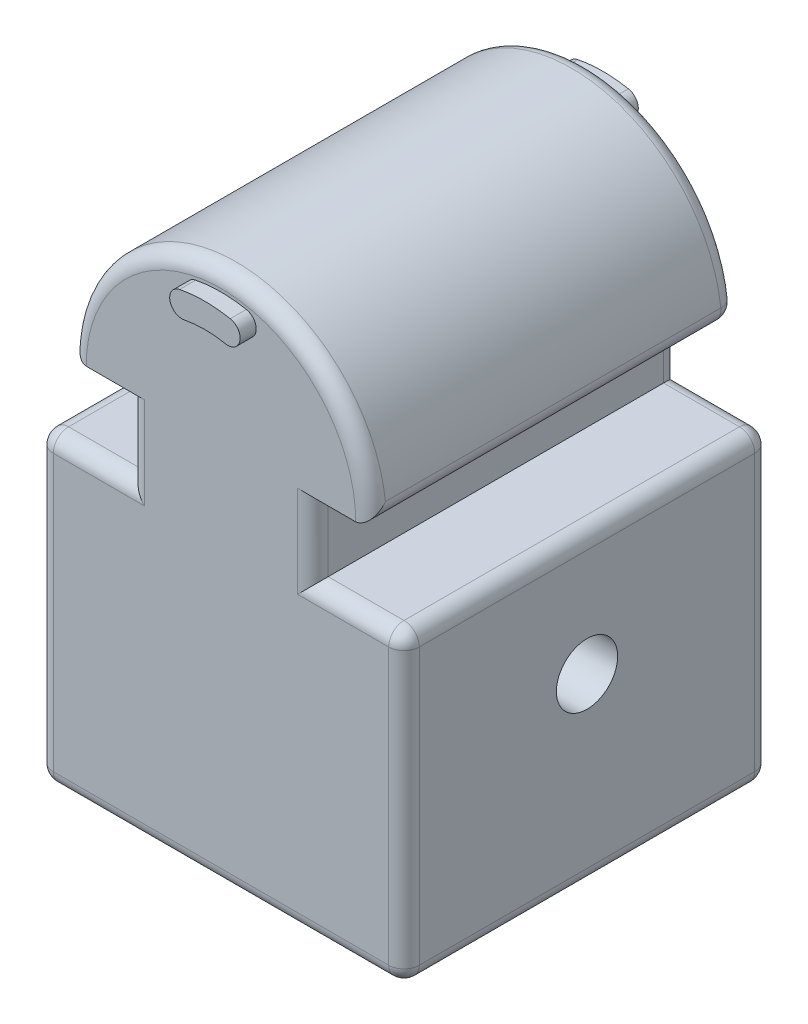
SolidWorks part; units mm, degrees
ref_plane "Front Plane" through (0, 0, 0) normal (0, 0, 1) x (1, 0, 0)
ref_plane "Top Plane" through (0, 0, 0) normal (0, 1, 0) x (1, 0, 0)
ref_plane "Right Plane" through (0, 0, 0) normal (1, 0, 0) x (0, 0, -1)
sketch "Sketch1" plane through (0, 0, 0) normal (0, 0, 1) x (1, 0, 0)
  line L0 (-12.446, 0) -> (12.446, 0)
  line L1 (0, 0) -> (-7.62, 0) construction
  line L2 (0, 9.906) -> (-1.905, 9.906) construction
  line L3 (-7.62, 0) -> (7.62, 0)
  line L7 (0, 9.906) -> (1.905, 9.906) construction
  line L8 (-7.62, -6.35) -> (-15.1765, -6.35)
  line L9 (7.62, -6.35) -> (15.1765, -6.35)
  line L10 (-7.62, -6.35) -> (-7.62, 0)
  line L12 (-15.1765, -6.35) -> (-15.1765, -31.75)
  line L15 (7.62, -6.35) -> (7.62, 0)
  line L16 (-15.1765, -31.75) -> (15.1765, -31.75)
  line L17 (15.1765, -31.75) -> (15.1765, -6.35)
  arc A0 (12.446, 0) -> (-12.446, 0) centre (0, 0) ccw
  arc A1 (8.636, 0) -> (-8.636, 0) centre (0, 0) ccw
  arc A2 (11.176, 0) -> (-11.176, 0) centre (0, 0) ccw
  arc A3 (11.049, 0) -> (-11.049, 0) centre (0, 0) ccw
  arc A4 (8.89, 0) -> (-8.89, 0) centre (0, 0) ccw
  circle A5 centre (0, 0) radius 11.176 construction
  circle A6 centre (0, 0) radius 11.049 construction
  circle A7 centre (0, 0) radius 8.89 construction
  circle A8 centre (0, 0) radius 8.636 construction
  arc A10 (9.906, 0) -> (-9.906, 0) centre (0, 0) ccw construction
  arc A11 (-1.905, 9.7211) -> (1.905, 9.7211) centre (0, 0) cw construction
  arc A12 (2.1004, 10.7181) -> (-2.1004, 10.7181) centre (0, 0) ccw
  arc A13 (1.7096, 8.7241) -> (-1.7096, 8.7241) centre (0, 0) ccw
  arc A14 (1.7096, 8.7241) -> (2.1004, 10.7181) centre (1.905, 9.7211) ccw
  arc A15 (-2.1004, 10.7181) -> (-1.7096, 8.7241) centre (-1.905, 9.7211) ccw
  arc A16 (-1.905, 9.7211) -> (1.905, 9.7211) centre (0, 0) cw construction
  arc A17 (2.1004, 10.7181) -> (-2.1004, 10.7181) centre (0, 0) ccw
  arc A18 (1.7096, 8.7241) -> (-1.7096, 8.7241) centre (0, 0) ccw
  arc A19 (1.7096, 8.7241) -> (2.1004, 10.7181) centre (1.905, 9.7211) ccw
  arc A20 (-2.1004, 10.7181) -> (-1.7096, 8.7241) centre (-1.905, 9.7211) ccw
  point P31 (0, 9.906)
  point P39 (0, 9.906)
  dimension "D1" = 24.892
  dimension "D2" = 22.352
  dimension "D3" = 17.272
  dimension "D8" = 9.906
  dimension "D11" = 8.89
  dimension "D12" = 10.922
  dimension "D4" = 7.62
  dimension "D7" = 0.254
  dimension "D9" = 1.905
  dimension "D10" = 1.905
  dimension "D14" = 7.5565
  dimension "D5" = 7.5565
extrude "Main Body Extrude" add sketch "Sketch1" along normal mid plane 30.353 contours L0 | A12 A15 A4 A14 | L0 A0 region at (0, 9.8081, 0) region at (0, -17.2796, 0)
extrude "Slot Extrude" add sketch "Sketch1<4>" along normal mid plane 33.02 contours A12 A15 A4 A14 region at (0, 9.8081, 0)
sketch "Sketch1<4>" plane through (0, 0, 0) normal (0, 0, 1) x (1, 0, 0) same geometry as "Sketch1"
sketch "Sketch2" plane through (0, -31.75, 0) normal (0, -1, 0) x (1, 0, 0)
  line L1 (-9.525, -9.525) -> (9.525, -9.525)
  line L2 (-9.525, -9.525) -> (-9.525, 9.525)
  line L3 (-9.525, 9.525) -> (9.525, 9.525)
  line L4 (9.525, -9.525) -> (9.525, 9.525)
  line L5 (-9.525, -9.525) -> (9.525, 9.525) construction
  line L6 (-9.525, 9.525) -> (9.525, -9.525) construction
  point P0 (0, 0)
  dimension "D1" = 19.05
  dimension "D2" = 19.05
extrude "Foot Connection Cut" cut sketch "Sketch2" against normal blind 22.86
sketch "Sketch4" plane through (-9.525, 0, 0) normal (1, 0, 0) x (0, 0, -1)
  line L0 (0, -8.89) -> (0, -16.51)
  line L5 (-9.525, -31.75) -> (9.525, -31.75)
  line L6 (9.525, -31.75) -> (9.525, -8.89)
  line L7 (9.525, -8.89) -> (-9.525, -8.89)
  line L8 (-9.525, -8.89) -> (-9.525, -31.75)
  line L9 (-9.525, -31.75) -> (9.525, -31.75)
  line L10 (9.525, -31.75) -> (9.525, -8.89)
  line L11 (9.525, -8.89) -> (-9.525, -8.89)
  line L12 (-9.525, -8.89) -> (-9.525, -31.75)
  circle A0 centre (0, -16.51) radius 2.54
  dimension "D3" = 5.08
  dimension "D1" = 7.62
  dimension "D2" = 0
extrude "Pinhole Cut" cut sketch "Sketch4" against normal mid plane 50.8 contours A0 region at (-9.525, -14.7647, -1.7453)
fillet "Fillet1" radius 1.27 24 edges at (11.3983, -6.35, 15.1765) (12.446, 0, 0) (15.1765, -6.35, 0) (7.62, -3.175, 15.1765) (-11.3982, -6.35, 15.1765) (-15.1765, -6.35, 0) (-7.62, -3.175, 15.1765) (-12.446, 0, 0) (0, 12.446, 15.1765) (11.3983, -6.35, -15.1765) (7.62, -3.175, -15.1765) (10.033, 0, -15.1765) (-10.033, 0, -15.1765) (-7.62, -3.175, -15.1765) (-11.3982, -6.35, -15.1765) (0, 12.446, -15.1765) (15.1765, -31.75, 0) (-15.1765, -31.75, 0) (0, -31.75, 15.1765) (0, -31.75, -15.1765) (-15.1765, -19.05, -15.1765) (-15.1765, -19.05, 15.1765) (15.1765, -19.05, 15.1765) (15.1765, -19.05, -15.1765)
chamfer "Chamfer2" distance 2.54 angle 45 4 edges at (-9.525, -20.32, -9.525) (-9.525, -20.32, 9.525) (9.525, -20.32, -9.525) (9.525, -20.32, 9.525)
chamfer "Chamfer1" distance 2.54 angle 45 8 edges at (9.525, -31.75, 0) (0, -31.75, -9.525) (0, -31.75, 9.525) (-9.525, -31.75, 0) (-8.255, -31.75, 8.255) (8.255, -31.75, 8.255) (8.255, -31.75, -8.255) (-8.255, -31.75, -8.255)
equation "\"InnerBaseDiameter\"=0.98"
equation "\"InnerBaseOuterGroove\"= \"InnerBaseDiameter\" - 0.1"
equation "\"InnerHingeInnerCurve\"= 1"
equation "\"InnerHingeOuterCurve\"= \"InnerHingeInnerCurve\" + 0.1"
equation "\"InnerBaseInnerGroove\"= \"InnerBaseOuterGroove\" - 0.2"
equation "\"InnerHingeWidth\"= 1.45"
equation "\"OuterBaseInnerGroove\"= \"OuterBaseOuterGroove\" - 0.25"
equation "\"OuterBaseDiameter\"= ( ( \"InnerHingeOuterCurve\" / 2 ) ^ 2 + ( \"InnerHingeLength\" / 2 ) ^ 2 ) ^ 0.5 * 2"
equation "\"InnerHingeLength\"=1.2"
equation "\"OuterBaseOuterGroove\"= \"OuterBaseDiameter\" - 0.2"
equation "\"D1@Sketch1\"=\"InnerBaseDiameter\""
equation "\"D2@Sketch1\"=\"InnerBaseOuterGroove\""
equation "\"D3@Sketch1\"=\"InnerBaseInnerGroove\""
equation "\"D8@Sketch1\"=\"InnerBaseOuterGroove\"  * 0.25 +\"InnerBaseInnerGroove\" * 0.25"
equation "\"D11@Sketch1\"=\"InnerBaseInnerGroove\" *0.5 +0.01"
equation "\"D12@Sketch1\"=\"InnerBaseOuterGroove\"*0.5 -0.01"
